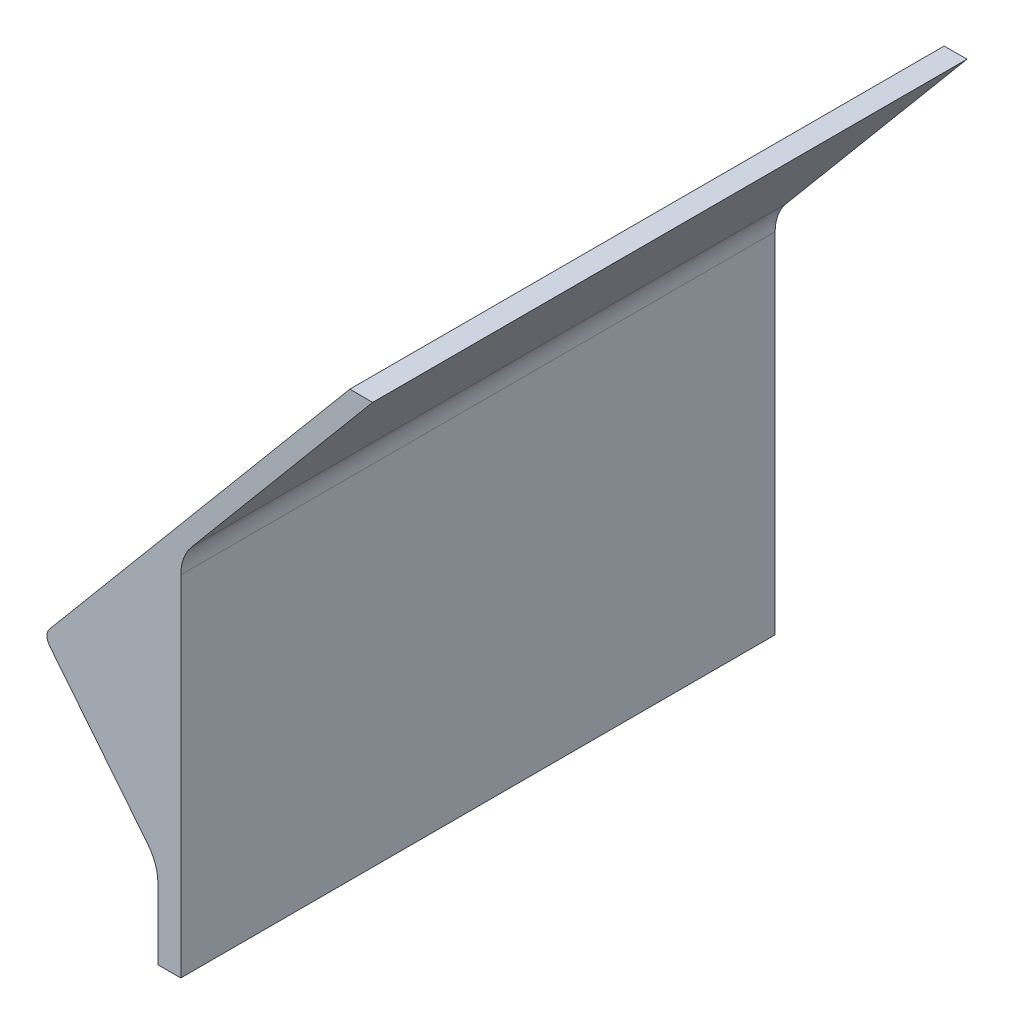
SolidWorks part; units mm, degrees
material "201 Annealed Stainless Steel (SS)"
ref_plane "Front Plane" through (0, 0, 0) normal (0, 0, 1) x (1, 0, 0)
ref_plane "Top Plane" through (0, 0, 0) normal (0, 1, 0) x (1, 0, 0)
ref_plane "Right Plane" through (0, 0, 0) normal (1, 0, 0) x (0, 0, -1)
sketch "Sketch1" plane through (0, 0, 0) normal (0, 0, 1) x (1, 0, 0)
  line L0 (0, 0) -> (0, 80)
  line L1 (0, 80) -> (41.974, 130.0227)
  line L2 (41.974, 130.0227) -> (36.974, 130.0227)
  line L3 (36.974, 130.0227) -> (-30, 50.2062)
  line L4 (-30, 50.2062) -> (-5, 18.9812)
  line L5 (-5, 18.9812) -> (-5, 0)
  line L6 (-5, 0) -> (0, 0)
  line L7 (-5, 0) -> (-45, 0) construction
  line L8 (-30, 0) -> (-30, 78.9136) construction
  dimension "D1" = 5
  dimension "D2" = 5
  dimension "D3" = 140
  dimension "D4" = 65.3
  dimension "D5" = 80
  dimension "D6" = 40
  dimension "D7" = 25
  dimension "D8" = 40
extrude "Funnel - Right Side" add sketch "Sketch1" along normal blind 130
fillet "Fillet2" radius 10 2 edges at (0, 80, 65) (-5, 18.9812, 65)
fillet "Fillet3" radius 2.5 1 edges at (-30, 50.2062, 65)
